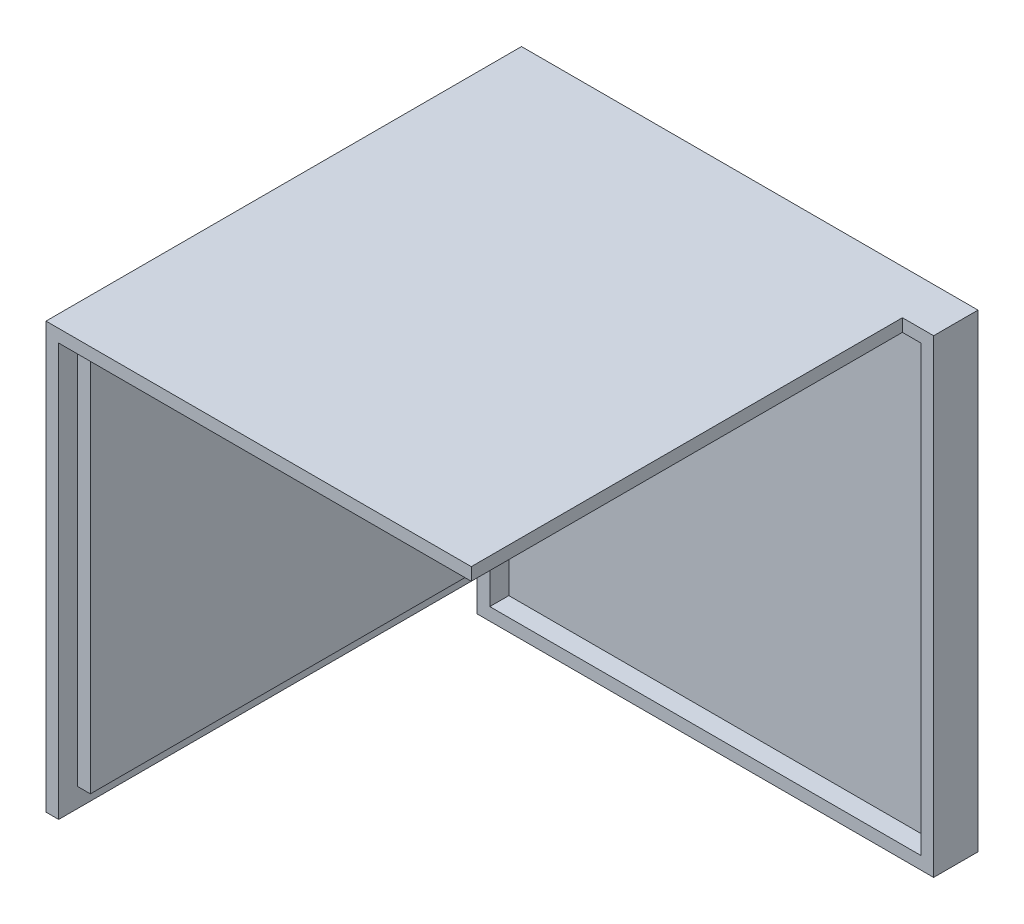
SolidWorks part; units mm, degrees
ref_plane "Alzado" through (0, 0, 0) normal (0, 0, 1) x (1, 0, 0)
ref_plane "Planta" through (0, 0, 0) normal (0, 1, 0) x (1, 0, 0)
ref_plane "Vista lateral" through (0, 0, 0) normal (1, 0, 0) x (0, 0, -1)
sketch "Croquis1" plane through (0, 0, 0) normal (0, 0, 1) x (1, 0, 0)
  line L0 (-476.9981, 176.8231) -> (-476.9981, 171.8231)
  line L1 (-464.6981, 176.8231) -> (-644.6981, 176.8231)
  line L2 (-464.6981, 176.8231) -> (-464.6981, -8.1769)
  line L3 (-464.6981, -8.1769) -> (-644.6981, -8.1769)
  line L4 (-644.6981, 176.8231) -> (-644.6981, -8.1769)
  line L5 (-469.6981, 171.8231) -> (-639.6981, 171.8231)
  line L6 (-469.6981, 171.8231) -> (-469.6981, -3.1769)
  line L7 (-469.6981, -3.1769) -> (-639.6981, -3.1769)
  line L8 (-639.6981, 171.8231) -> (-639.6981, -3.1769)
  line L9 (-484.4981, 171.8231) -> (-484.4981, 166.8231)
  line L10 (-474.6981, 166.8231) -> (-634.6981, 166.8231)
  line L11 (-474.6981, 166.8231) -> (-474.6981, 6.8231)
  line L12 (-474.6981, 6.8231) -> (-634.6981, 6.8231)
  line L13 (-634.6981, 166.8231) -> (-634.6981, 6.8231)
  line L14 (-639.6981, 9.1231) -> (-644.6981, 9.1231)
  line L15 (-634.6981, 16.6231) -> (-639.6981, 16.6231)
  line L16 (-474.6981, 166.8231) -> (-634.6981, 6.8231) construction
  line L17 (-474.6981, 6.8231) -> (-634.6981, 166.8231) construction
  circle A0 centre (-554.6981, 86.8231) radius 25 construction
  circle A2 centre (-554.6981, 86.8231) radius 37 construction
  dimension "D1" = 185
  dimension "D2" = 180
  dimension "D3" = 5
  dimension "D4" = 5
  dimension "D5" = 5
  dimension "D6" = 5
  dimension "D7" = 12.3
  dimension "D8" = 160
  dimension "D9" = 160
  dimension "D10" = 5
  dimension "D11" = 5
  dimension "D12" = 14.8
  dimension "D13" = 17.3
  dimension "D14" = 19.8
extrude "Saliente-Extruir1" add sketch "Croquis1" against normal blind 10 contours L3 L4 L1 L2
extrude "Saliente-Extruir2" add sketch "Croquis1<3>" along normal blind 7.5 contours L8 L14 L4 L3 L2 L1 L0 L5 L6 L7 region at (-470.8481, 174.2419, 0)
sketch "Croquis1<3>" plane through (0, 0, 0) normal (0, 0, 1) x (1, 0, 0) same geometry as "Croquis1"
extrude "Saliente-Extruir3" add sketch "Croquis1<5>" along normal blind 170 contours L15 L13 L10 L9 L5 L8 region at (-486.6929, 169.3231, 0)
sketch "Croquis1<5>" plane through (0, 0, 0) normal (0, 0, 1) x (1, 0, 0) same geometry as "Croquis1"
extrude "Saliente-Extruir4" add sketch "Croquis1<6>" along normal blind 177.5 contours L14 L8 L5 L0 L1 L4 region at (-479.3697, 174.3231, 0)
sketch "Croquis1<6>" plane through (0, 0, 0) normal (0, 0, 1) x (1, 0, 0) same geometry as "Croquis1"
